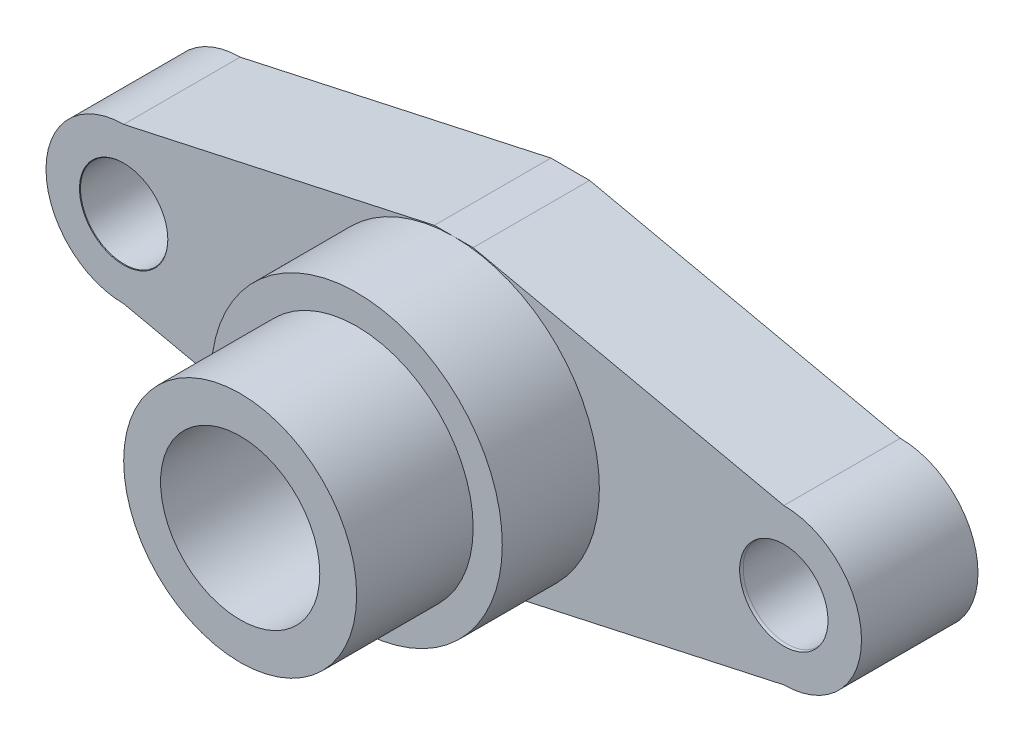
SolidWorks part; units mm, degrees
ref_plane "Front Plane" through (0, 0, 0) normal (0, 0, 1) x (1, 0, 0)
ref_plane "Top Plane" through (0, 0, 0) normal (0, 1, 0) x (1, 0, 0)
ref_plane "Right Plane" through (0, 0, 0) normal (1, 0, 0) x (0, 0, -1)
sketch "Sketch1" plane through (0, 0, 0) normal (0, 0, 1) x (1, 0, 0)
  line L0 (0, -0.7604) -> (0, 9.0891) construction
  line L1 (17, 4) -> (0.9966, 7.5)
  line L2 (17, -4) -> (0.9966, -7.5)
  line L5 (0, 0) -> (5.9435, 0) construction
  line L6 (-17, -4) -> (-0.9966, -7.5)
  line L7 (-17, 4) -> (-0.9966, 7.5)
  line L8 (-0.9966, 7.5) -> (0.9966, 7.5)
  line L9 (-0.9966, -7.5) -> (0.9966, -7.5)
  arc A0 (17, -4) -> (17, 4) centre (17, 0) ccw
  arc A2 (-17, -4) -> (-17, 4) centre (-17, 0) cw
  point P10 (0, -9.4844)
  dimension "D1" = 8
  dimension "D2" = 7.5
  dimension "D3" = 7.5
  dimension "D4" = 17
extrude "Boss-Extrude1" add sketch "Sketch1" along normal blind 6
sketch "Sketch2" plane through (0, 0, 6) normal (0, 0, 1) x (1, 0, 0)
  circle A1 centre (0, 0) radius 7.5
  dimension "D1" = 15
extrude "Boss-Extrude2" add sketch "Sketch2" along normal blind 5 and the other way up to surface (6 mm away) other way up to face at (0, 0, 0)
sketch "Sketch3" plane through (0, 0, 11) normal (0, 0, 1) x (1, 0, 0)
  circle A0 centre (0, 0) radius 6
  dimension "D1" = 12
extrude "Boss-Extrude3" add sketch "Sketch3" along normal blind 6
sketch "Sketch4" plane through (0, 0, 17) normal (0, 0, 1) x (1, 0, 0)
  circle A0 centre (0, 0) radius 4.1
  dimension "D1" = 8.2
extrude "Cut-Extrude1" cut sketch "Sketch4" against normal offset from surface (14 mm away) 3 up to face at (0, 0, 0)
hole_wizard "M4 Clearance Hole1" positions "3DSketch1" profile "Sketch6" hole size "M4" standard "AS" end condition through all
sketch3d "3DSketch1"
  line L0 (17, 0, 6) -> (17, 0, 0) construction
  line L1 (-17, 0, 6) -> (-17, 0, 0) construction
  point P0 (17, 0, 6)
  point P10 (-17, 0, 6)
sketch "Sketch6" plane through (17, 0, 6) normal (1, 0, 0) x (0, -1, 0)
  line L0 (0, 0) -> (0, 6)
  line L1 (0, 6) -> (2.25, 6)
  line L2 (2.25, 6) -> (2.25, 0.025)
  line L3 (2.25, 0.025) -> (2.275, 0)
  line L5 (2.275, 0) -> (0, 0)
  line L6 (-2.25, 0.025) -> (-2.275, 0) construction
  line L11 (0, -6.35) -> (0, 107.95) construction
  dimension "Thru Hole Dia." = 4.5
  dimension "Thru Hole Depth" = 6
  dimension "Near C'Sink Dia." = 4.55
  dimension "Near C'Sink Angle" = 90
fillet "Fillet4" radius 0.5 1 edges at (19.25, 0, 5.975)
